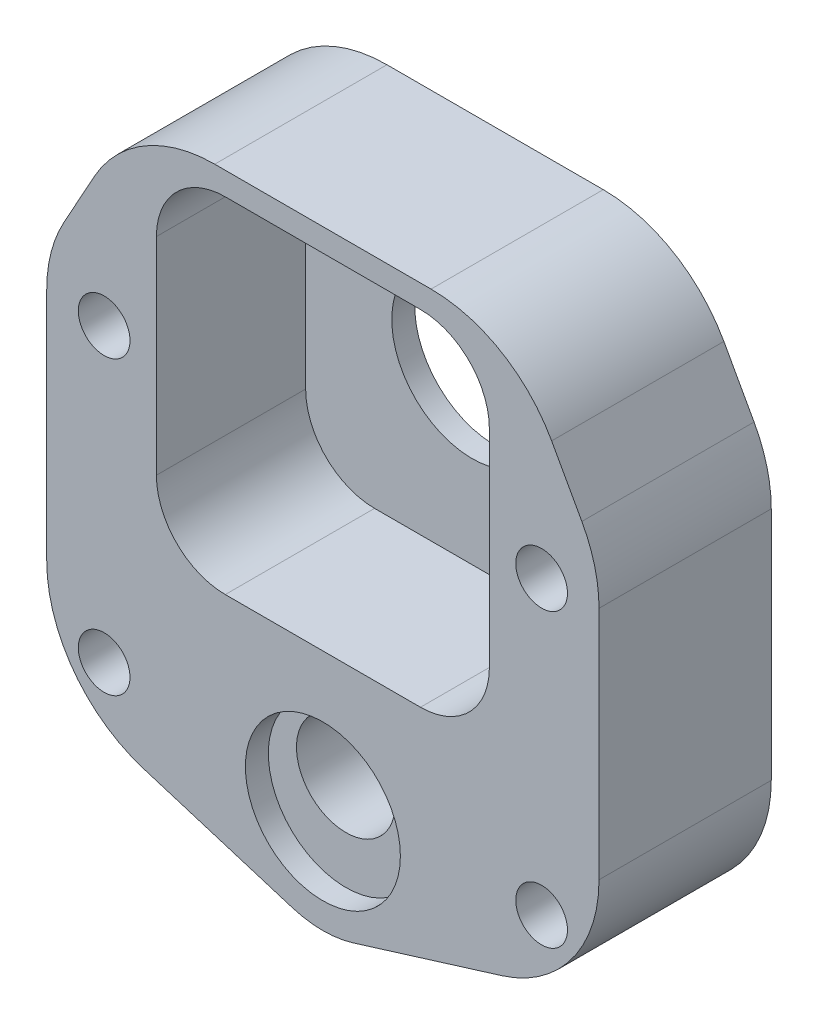
SolidWorks part; units mm, degrees
ref_plane "Front Plane" through (0, 0, 0) normal (0, 0, 1) x (1, 0, 0)
ref_plane "Top Plane" through (0, 0, 0) normal (0, 1, 0) x (1, 0, 0)
ref_plane "Right Plane" through (0, 0, 0) normal (1, 0, 0) x (0, 0, -1)
sketch "Sketch2" plane through (0, 0, 0) normal (0, 0, 1) x (1, 0, 0)
  line L0 (14.5, 15) -> (-14.5, 15)
  line L1 (14.5, 15) -> (14.5, -15)
  line L2 (14.5, -15) -> (-14.5, -15)
  line L3 (-14.5, 15) -> (-14.5, -15)
  line L4 (-16.75, -42) -> (16.75, -42)
  line L5 (-16.75, -42) -> (-16.75, 16)
  line L6 (-16.75, 16) -> (16.75, 16)
  line L7 (16.75, -42) -> (16.75, 16)
  circle A0 centre (0, 0) radius 7
  circle A1 centre (0, -25.4) radius 4.3
  circle A2 centre (0, -27.1) radius 6.75
  point P15 (0, 0)
  point P17 (0, 0)
  point P18 (0, 0)
  dimension "D2" = 14
  dimension "D6" = 13.5
  dimension "D7" = 8.6
  dimension "D1" = 29
  dimension "D3" = 30
  dimension "D4" = 58
  dimension "D5" = 33.5
  dimension "D8" = 1.7
  dimension "D9" = 16.75
  dimension "D10" = 14.5
  dimension "D11" = 16
  dimension "D12" = 15
  dimension "D13" = 10.4
sketch "Sketch3" plane through (0, 0, 0) normal (0, 0, 1) x (1, 0, 0)
  line L0 (14.5, 15) -> (-14.5, 15) construction
  line L1 (-14.5, 15) -> (-14.5, -15) construction
  line L2 (14.5, -15) -> (-14.5, -15) construction
  line L3 (14.5, 15) -> (14.5, -15) construction
  line L4 (14.5, 15) -> (-14.5, 15)
  line L5 (-14.5, 15) -> (-14.5, -15)
  line L6 (14.5, -15) -> (-14.5, -15)
  line L7 (14.5, 15) -> (14.5, -15)
  line L8 (-16.5, 17) -> (16.5, 17)
  line L9 (16.5, 17) -> (24.05, 3.3333)
  line L10 (24.05, 3.3333) -> (24.05, -29.0882)
  line L11 (24.05, -29.0882) -> (2.6571, -35.6988)
  line L12 (-16.5, 17) -> (-24.05, 3.3333)
  line L13 (-24.05, 3.3333) -> (-24.05, -29.0882)
  line L14 (-24.05, -29.0882) -> (-2.6571, -35.6988)
  line L15 (-19.05, -25.4) -> (19.05, 0) construction
  line L16 (-19.05, 0) -> (19.05, -25.4) construction
  circle A0 centre (0, -27.1) radius 6.75 construction
  circle A1 centre (0, -25.4) radius 4.3 construction
  circle A2 centre (0, 0) radius 7 construction
  circle A3 centre (0, -27.1) radius 6.75
  circle A4 centre (0, -25.4) radius 4.3
  circle A5 centre (0, 0) radius 7
  circle A6 centre (19.05, 0) radius 2.25
  circle A7 centre (-19.05, 0) radius 2.25
  circle A8 centre (-19.05, -25.4) radius 2.25
  circle A9 centre (19.05, -25.4) radius 2.25
  circle A10 centre (0, -27.1) radius 9
  point P24 (0, 0)
  point P31 (0, 0)
  point P32 (0, 0)
  point P33 (-15.437, 17)
  point P34 (17.6036, 17)
  dimension "D2" = 4.5
  dimension "D5" = 18
  dimension "D6" = 25.4
  dimension "D7" = 38.1
  dimension "D8" = 2
  dimension "D1" = 19.05
  dimension "D9" = 5
  dimension "D10" = 5
  dimension "D11" = 5
  dimension "D12" = 5
  dimension "D13" = 2
  dimension "D14" = 2
  dimension "D3" = 2
  dimension "D4" = 2
extrude "Boss-Extrude1" add sketch "Sketch3" along normal blind 15 contours A10 L11 L10 L9 L8 L12 L13 L14 A9 A8 A7 A6 L4 L7 L6 L5 | A10 A3 | A3 A4 region at (0, 16.2865, 0) region at (-5.1915, -20.0621, 0) region at (-6.5591, -27.1, 0)
extrude "Boss-Extrude2" add sketch "Sketch3<3>" along normal blind 2 contours L7 L4 L5 L6 A5 region at (14.0827, 0, 0)
sketch "Sketch3<3>" plane through (0, 0, 0) normal (0, 0, 1) x (1, 0, 0) same geometry as "Sketch3"
extrude "Cut-Extrude1" cut sketch "Sketch3<4>" against normal blind 2 from surface contours A3 A4 region at (-6.5591, -27.1, 0) starting at face at (0, -11.1636, 15)
sketch "Sketch3<4>" plane through (0, 0, 0) normal (0, 0, 1) x (1, 0, 0) same geometry as "Sketch3"
fillet "Fillet1" radius 6 4 edges at (-14.5, -15, 8.5) (-14.5, 15, 8.5) (14.5, 15, 8.5) (14.5, -15, 8.5)
fillet "Fillet2" radius 12 6 edges at (24.05, 3.3333, 7.5) (24.05, -29.0882, 7.5) (-24.05, -29.0882, 7.5) (-24.05, 3.3333, 7.5) (16.5, 17, 7.5) (-16.5, 17, 7.5)
